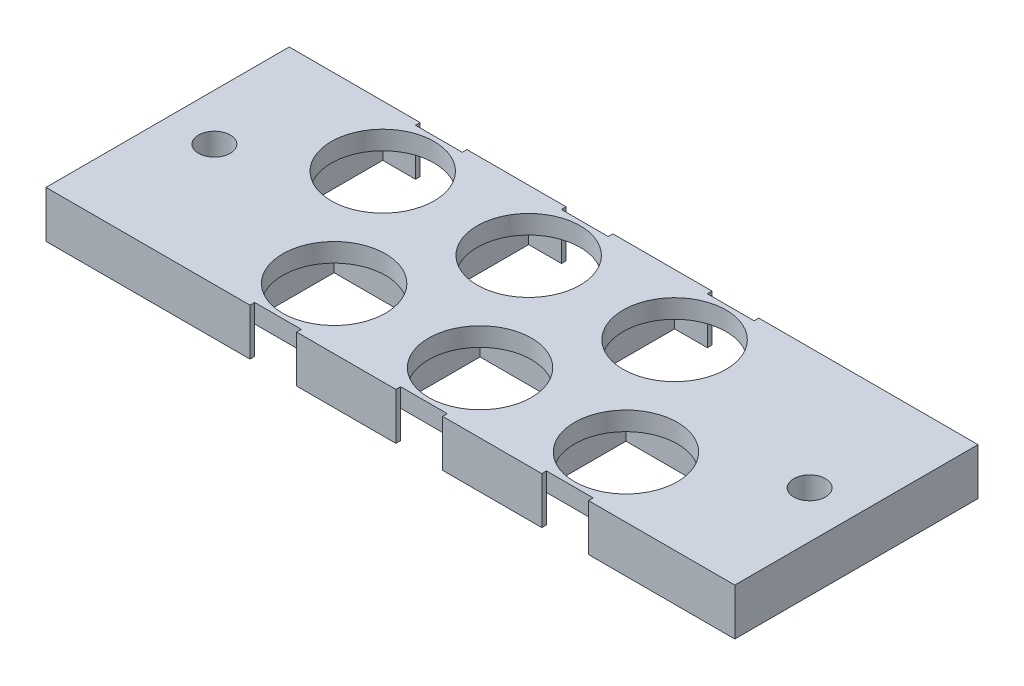
SolidWorks part; units mm, degrees
ref_plane "Front Plane" through (0, 0, 0) normal (0, 0, 1) x (1, 0, 0)
ref_plane "Top Plane" through (0, 0, 0) normal (0, 1, 0) x (1, 0, 0)
ref_plane "Right Plane" through (0, 0, 0) normal (1, 0, 0) x (0, 0, -1)
sketch "Sketch1" plane through (0, 0, 0) normal (0, 1, 0) x (1, 0, 0)
  line L0 (3.7864, -4.1649) -> (6.3864, -4.1649)
  line L1 (19.3864, -4.1649) -> (21.9864, -4.1649)
  line L2 (27.1864, -30.1649) -> (29.7864, -30.1649)
  line L3 (11.5864, -30.1649) -> (14.1864, -30.1649)
  line L4 (42.7864, -30.1649) -> (54.419, -30.1649)
  line L5 (54.419, -30.1649) -> (54.419, -4.1649)
  line L6 (54.419, -4.1649) -> (34.9864, -4.1649)
  line L7 (-9.2136, -4.1649) -> (-19.2136, -4.1649)
  line L8 (-19.2136, -4.1649) -> (-19.2136, -30.1649)
  line L9 (-19.2136, -30.1649) -> (-1.4136, -30.1649)
  line L10 (-14.2136, -4.1649) -> (-14.2136, -30.1649) construction
  line L11 (49.419, -4.1649) -> (49.419, -30.1649) construction
  circle A0 centre (-14.2136, -17.1649) radius 1.7
  circle A1 centre (49.419, -17.1649) radius 1.7
  line B0 (34.9864, -17.1649) -> (34.9864, -4.1649)
  line B1 (11.5864, -30.1649) -> (7.5864, -30.1649)
  line B2 (-0.9136, -29.6649) -> (11.0864, -29.6649)
  line B3 (11.5864, -30.1649) -> (11.5864, -17.1649)
  line B4 (27.1864, -30.1649) -> (27.1864, -17.1649)
  line B5 (42.7864, -30.1649) -> (42.7864, -17.1649)
  line B6 (-1.4136, -17.1649) -> (-1.4136, -30.1649)
  line B7 (11.0864, -29.6649) -> (11.0864, -17.6649)
  line B8 (29.7864, -17.1649) -> (29.7864, -30.1649)
  line B9 (21.9864, -4.1649) -> (21.9864, -17.1649)
  line B10 (34.4864, -16.6649) -> (34.4864, -4.6649)
  line B11 (18.8864, -16.6649) -> (18.8864, -4.6649)
  line B12 (3.7864, -17.1649) -> (3.7864, -4.1649)
  line B13 (42.2864, -29.6649) -> (42.2864, -17.6649)
  line B14 (14.6864, -29.6649) -> (26.6864, -29.6649)
  line B15 (30.2864, -17.6649) -> (30.2864, -29.6649)
  line B16 (30.2864, -17.6649) -> (42.2864, -29.6649) construction
  line B17 (14.6864, -17.6649) -> (26.6864, -29.6649) construction
  line B18 (-0.9136, -17.6649) -> (11.0864, -29.6649) construction
  line B19 (42.7864, -17.1649) -> (29.7864, -17.1649)
  line B20 (3.2864, -16.6649) -> (3.2864, -4.6649)
  line B21 (14.6864, -17.6649) -> (14.6864, -29.6649)
  line B22 (27.1864, -30.1649) -> (23.1864, -30.1649)
  line B23 (29.7864, -30.1649) -> (33.7864, -30.1649)
  line B24 (42.7864, -30.1649) -> (38.7864, -30.1649)
  line B25 (-8.7136, -10.6649) -> (3.2864, -10.6649) construction
  line B26 (6.8864, -10.6649) -> (18.8864, -10.6649) construction
  line B27 (22.4864, -10.6649) -> (34.4864, -10.6649) construction
  line B28 (-0.9136, -23.6649) -> (11.0864, -23.6649) construction
  line B29 (14.6864, -23.6649) -> (26.6864, -23.6649) construction
  line B30 (30.2864, -23.6649) -> (42.2864, -23.6649) construction
  line B31 (-27.4152, -23.6649) -> (51.2342, -23.6649) construction
  line B32 (21.9864, -17.1649) -> (34.9864, -17.1649)
  line B33 (-27.4152, -10.6649) -> (51.2342, -10.6649) construction
  line B34 (28.4864, -16.6649) -> (28.4864, -4.6649) construction
  line B35 (36.2864, -17.6649) -> (36.2864, -29.6649) construction
  line B36 (20.6864, -17.6649) -> (20.6864, -29.6649) construction
  line B37 (12.8864, -16.6649) -> (12.8864, -4.6649) construction
  line B38 (5.0864, -17.6649) -> (5.0864, -29.6649) construction
  line B39 (-2.7136, -16.6649) -> (-2.7136, -4.6649) construction
  line B40 (22.4864, -4.6649) -> (22.4864, -16.6649)
  line B41 (22.4864, -16.6649) -> (34.4864, -16.6649)
  line B42 (34.4864, -4.6649) -> (22.4864, -4.6649)
  line B43 (34.4864, -16.6649) -> (22.4864, -4.6649) construction
  line B44 (34.4864, -4.6649) -> (22.4864, -16.6649) construction
  line B45 (34.9864, -4.1649) -> (30.9864, -4.1649)
  line B46 (21.9864, -4.1649) -> (25.9864, -4.1649)
  line B47 (30.9864, -4.1649) -> (30.9864, -4.6649)
  line B48 (25.9864, -4.1649) -> (25.9864, -4.6649)
  circle B49 centre (28.4864, -10.6649) radius 5.5
  line B50 (-0.9136, -17.6649) -> (-0.9136, -29.6649)
  line B51 (11.0864, -17.6649) -> (-0.9136, -17.6649)
  line B52 (-0.9136, -29.6649) -> (11.0864, -17.6649) construction
  line B53 (11.5864, -17.1649) -> (-1.4136, -17.1649)
  line B54 (-1.4136, -30.1649) -> (2.5864, -30.1649)
  line B55 (2.5864, -30.1649) -> (2.5864, -29.6649)
  line B56 (7.5864, -30.1649) -> (7.5864, -29.6649)
  circle B57 centre (5.0864, -23.6649) radius 5.5
  line B58 (26.6864, -29.6649) -> (26.6864, -17.6649)
  line B59 (26.6864, -17.6649) -> (14.6864, -17.6649)
  line B60 (14.6864, -29.6649) -> (26.6864, -17.6649) construction
  line B61 (27.1864, -17.1649) -> (14.1864, -17.1649)
  line B62 (14.1864, -17.1649) -> (14.1864, -30.1649)
  line B63 (14.1864, -30.1649) -> (18.1864, -30.1649)
  line B64 (18.1864, -30.1649) -> (18.1864, -29.6649)
  line B65 (23.1864, -30.1649) -> (23.1864, -29.6649)
  circle B66 centre (20.6864, -23.6649) radius 5.5
  line B67 (42.2864, -17.6649) -> (30.2864, -17.6649)
  line B68 (30.2864, -29.6649) -> (42.2864, -29.6649)
  line B69 (30.2864, -29.6649) -> (42.2864, -17.6649) construction
  line B70 (33.7864, -30.1649) -> (33.7864, -29.6649)
  line B71 (38.7864, -30.1649) -> (38.7864, -29.6649)
  circle B72 centre (36.2864, -23.6649) radius 5.5
  line B73 (6.8864, -4.6649) -> (6.8864, -16.6649)
  line B74 (6.8864, -16.6649) -> (18.8864, -16.6649)
  line B75 (18.8864, -4.6649) -> (6.8864, -4.6649)
  line B76 (18.8864, -16.6649) -> (6.8864, -4.6649) construction
  line B77 (18.8864, -4.6649) -> (6.8864, -16.6649) construction
  line B78 (6.3864, -17.1649) -> (19.3864, -17.1649)
  line B79 (19.3864, -17.1649) -> (19.3864, -4.1649)
  line B80 (6.3864, -4.1649) -> (6.3864, -17.1649)
  line B81 (19.3864, -4.1649) -> (15.3864, -4.1649)
  line B82 (6.3864, -4.1649) -> (10.3864, -4.1649)
  line B83 (15.3864, -4.1649) -> (15.3864, -4.6649)
  line B84 (10.3864, -4.1649) -> (10.3864, -4.6649)
  circle B85 centre (12.8864, -10.6649) radius 5.5
  line B86 (-8.7136, -4.6649) -> (-8.7136, -16.6649)
  line B87 (-8.7136, -16.6649) -> (3.2864, -16.6649)
  line B88 (3.2864, -4.6649) -> (-8.7136, -4.6649)
  line B89 (3.2864, -16.6649) -> (-8.7136, -4.6649) construction
  line B90 (3.2864, -4.6649) -> (-8.7136, -16.6649) construction
  line B91 (-9.2136, -17.1649) -> (3.7864, -17.1649)
  line B92 (-9.2136, -4.1649) -> (-9.2136, -17.1649)
  line B93 (3.7864, -4.1649) -> (-0.2136, -4.1649)
  line B94 (-9.2136, -4.1649) -> (-5.2136, -4.1649)
  line B95 (-0.2136, -4.1649) -> (-0.2136, -4.6649)
  line B96 (-5.2136, -4.1649) -> (-5.2136, -4.6649)
  circle B97 centre (-2.7136, -10.6649) radius 5.5
  dimension "D1" = 5
  dimension "D2" = 10
  dimension "D3" = 5
sketch_block_instance "Block1-5"
sketch_block "Block1" parameters "D3"=6, "D1"=12, "D2"=12, "D4"=12, "D5"=78.6494, "D6"=78.6494, "D7"=78.6494, "D8"=10.3235, "D9"=14.0261, "D10"=17.7654, "D11"=23.7534, "D12"=22.7743, "D13"=52
sketch_block_instance "Block2-2"
sketch_block "Block2" parameters "D2"=8, "D1"=12
sketch_block_instance "Block2-3"
sketch_block_instance "Block2-4"
sketch_block_instance "Block2-5"
sketch_block_instance "Block2-6"
sketch_block_instance "Block2-7"
sketch_block_instance "Block3-1"
sketch_block "Block3"
sketch_block_instance "Block4-1"
sketch_block "Block4"
sketch_block_instance "Block5-1"
sketch_block "Block5"
sketch_block_instance "Block6-1"
sketch_block "Block6"
sketch_block_instance "Block7-1"
sketch_block "Block7"
sketch_block_instance "Block8-1"
sketch_block "Block8"
extrude "Boss-Extrude1" add sketch "Sketch1" against normal blind 2 contours B20 B88 B86 B87 B97 | B11 B75 B73 B74 B85 | B50 B2 B7 B51 B57 | B21 B14 B58 B59 B66 | B10 B42 B40 B41 B49 | B15 B68 B13 B67 B72 region at (1.5364, 0, 4.8346) region at (12.8864, 0, 4.8346) region at (0.8364, 0, 29.4952) region at (16.4364, 0, 29.4952) region at (28.4864, 0, 4.8346) region at (32.0364, 0, 29.4952)
extrude "Boss-Extrude2" add sketch "Sketch1<3>" against normal blind 5 contours B92 L7 L8 L9 B6 B91 A0 | B56 B1 B3 B53 B6 B54 B55 B2 B50 B51 B7 | B96 B94 B92 B91 B53 B12 B93 B95 B88 B20 B87 B86 | B12 B53 B80 L0 | B84 B82 B80 B53 B78 B61 B79 B81 B83 B75 B11 B74 B73 | B78 B3 L3 B62 | B79 B61 B9 L1 | B8 B32 B4 L2 | B65 B22 B4 B32 B61 B62 B63 B64 B14 B21 B59 B58 | B48 B46 B9 B32 B0 B45 B47 B42 B10 B41 B40 | B71 B24 B5 B19 B32 B8 B23 B70 B68 B15 B67 B13 | B5 L4 L5 L6 B0 B19 A1 region at (5.0864, 0, 10.6649) region at (3.6025, 0, 10.6649) region at (8.3864, 0, 4.3487) region at (5.0864, 0, 17.3487) region at (-11.6521, 0, 19.0356) region at (12.8864, 0, 23.6649) region at (16.7864, 0, 17.3487) region at (20.6864, 0, 10.6649) region at (22.1702, 0, 10.6649) region at (28.4864, 0, 23.6649) region at (32.3864, 0, 17.3487) region at (46.0882, 0, 15.4953)
sketch "Sketch1<3>" plane through (0, 0, 0) normal (0, 1, 0) x (1, 0, 0) same geometry as "Sketch1"
sketch "Sketch2" plane through (0, -5, 0) normal (0, -1, 0) x (-1, 0, 0)
  text T0 "F5"
extrude "Cut-Extrude1" cut sketch "Sketch2" against normal blind 1
